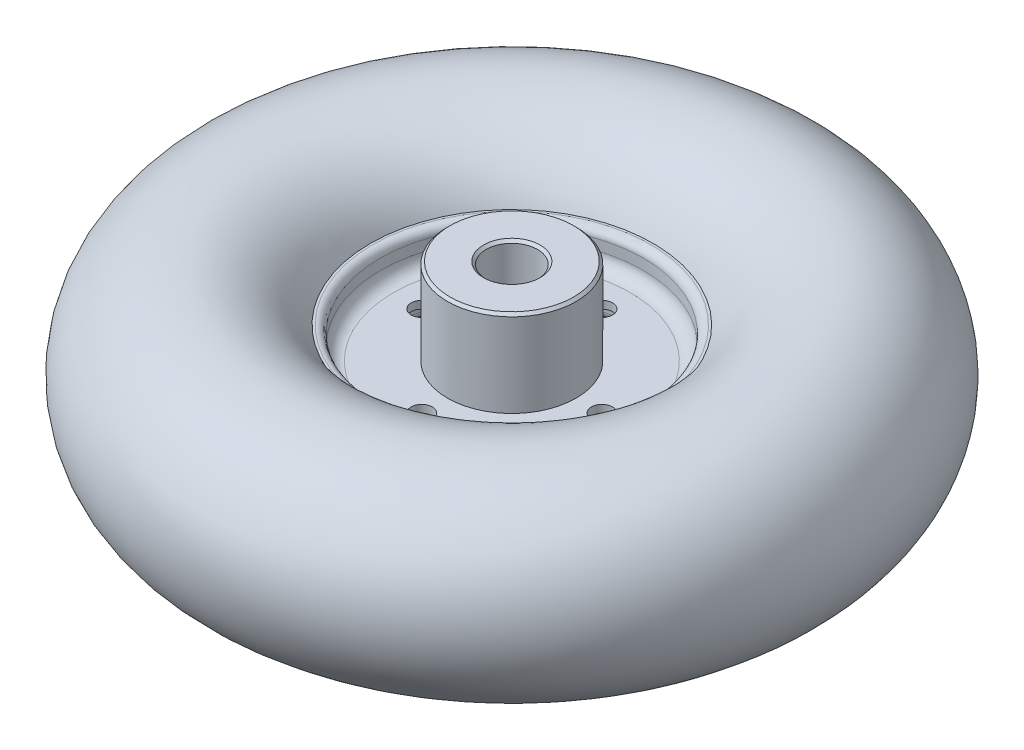
SolidWorks part; units mm, degrees
ref_plane "前视基准面" through (0, 0, 0) normal (0, 0, 1) x (1, 0, 0)
ref_plane "上视基准面" through (0, 0, 0) normal (0, 1, 0) x (1, 0, 0)
ref_plane "右视基准面" through (0, 0, 0) normal (1, 0, 0) x (0, 0, -1)
sketch "草图1" plane through (0, 0, 0) normal (0, 0, 1) x (1, 0, 0)
  line L0 (0, 112.942) -> (0, -122.985) construction
  line L1 (0, 0) -> (239.8897, 0) construction
  line L2 (89.5, 51.1291) -> (89.5, -70.8646) construction
  line L3 (89.5, -9.8677) -> (0, -5.0215) construction
  line L4 (-969.5, -6.673) -> (49030.5, -6.673) construction
  line L5 (51, -23.0538) -> (61, -23.0538)
  line L6 (51, -23.0538) -> (51, 6.9462)
  line L7 (51, 6.9462) -> (61, 6.9462)
  line L8 (61, -23.0538) -> (61, 6.9462)
  line L9 (51, -23.0538) -> (61, 6.9462) construction
  line L10 (51, 6.9462) -> (61, -23.0538) construction
  line L11 (10, -8.173) -> (51, -8.173)
  line L12 (10, -8.173) -> (10, -5.173)
  line L13 (10, -5.173) -> (51, -5.173)
  line L14 (51, -8.173) -> (51, -5.173)
  line L15 (10, -8.173) -> (51, -5.173) construction
  line L16 (10, -5.173) -> (51, -8.173) construction
  circle A0 centre (89.5, -9.8677) radius 38.5
  point P9 (56, -8.0538)
  point P15 (30.5, -6.673)
  dimension "D1" = 77
  dimension "D2" = 89.5
  dimension "D3" = 10
  dimension "D4" = 56
  dimension "D5" = 30
  dimension "D6" = 20
  dimension "D7" = 3
revolve "旋转1" add sketch "草图1" angle 360 about L0 region at (51.6948, -19.7775, 0) region at (56.466, -8.4685, 0) region at (91.5227, -9.9534, 0) region at (52.149, 2.7861, 0) region at (30.5, -6.673, 0)
fillet "圆角1" radius 3 2 edges at (-51, -23.0538, 0) (-51, 6.9462, 0)
fillet "圆角2" radius 5 2 edges at (-51, -8.173, 0) (-51, -5.173, 0)
ref_plane "基准面1" through (0, -6.673, 0) normal (0, -1, 0) x (-1, 0, 0)
sketch "草图3" plane through (0, -6.673, 0) normal (0, -1, 0) x (-1, 0, 0)
  circle A0 centre (0, 0) radius 25
  circle A1 centre (0, 0) radius 10 construction
  circle A2 centre (0, 0) radius 10
  dimension "D1" = 50
extrude "凸台-拉伸1" add sketch "草图3" along normal blind 35 and the other way blind 35
chamfer "倒角1" distance 1 angle 45 4 edges at (10, -41.673, 0) (25, -41.673, 0) (10, 28.327, 0) (25, 28.327, 0)
sketch "草图4" plane through (0, -5.173, 0) normal (0, 1, 0) x (1, 0, 0)
  circle A0 centre (35, 0) radius 4.1
  circle A1 centre (0, 0) radius 10 construction
  dimension "D1" = 8.2
  dimension "D2" = 0
  dimension "D3" = 35
extrude "切除-拉伸1" cut sketch "草图4" against normal blind 10
pattern_circular "阵列(圆周)1" count 4 every 90 about axis through (0, 112.942, 0) along (0, 1, 0) of "切除-拉伸1"
